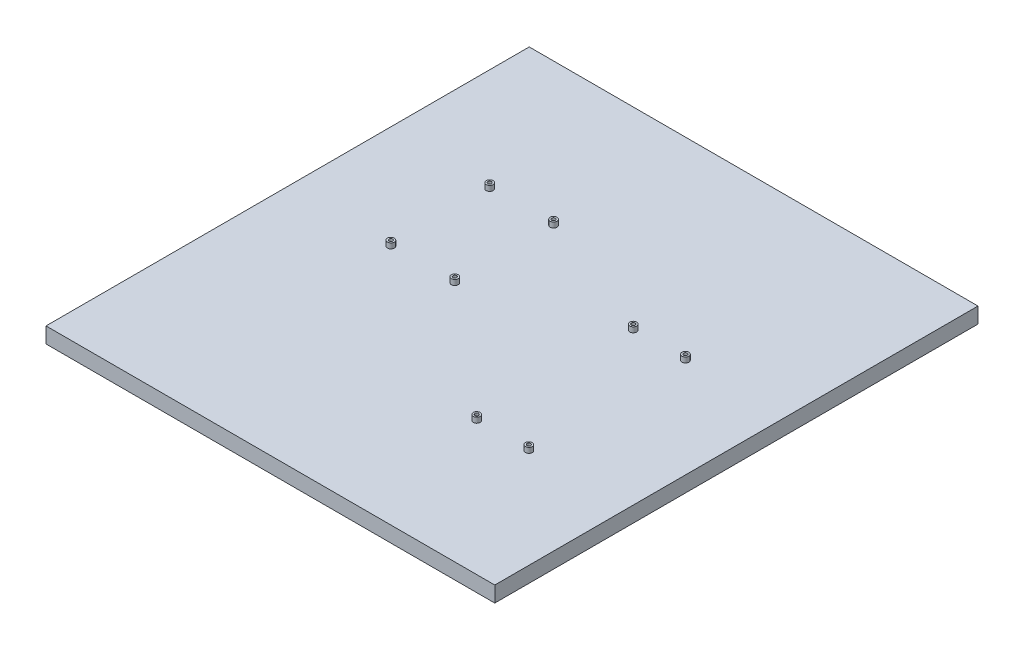
SolidWorks part; units mm, degrees
ref_plane "Front Plane" through (0, 0, 0) normal (0, 0, 1) x (1, 0, 0)
ref_plane "Top Plane" through (0, 0, 0) normal (0, 1, 0) x (1, 0, 0)
ref_plane "Right Plane" through (0, 0, 0) normal (1, 0, 0) x (0, 0, -1)
sketch "Sketch1" plane through (0, 0, 0) normal (0, 1, 0) x (1, 0, 0)
  line L1 (-215, -231.5) -> (215, -231.5)
  line L2 (-215, -231.5) -> (-215, 231.5)
  line L3 (-215, 231.5) -> (215, 231.5)
  line L4 (215, -231.5) -> (215, 231.5)
  line L5 (-215, -231.5) -> (215, 231.5) construction
  line L6 (-215, 231.5) -> (215, -231.5) construction
  point P0 (0, 0)
  dimension "D1" = 430
  dimension "D2" = 463
extrude "Boss-Extrude1" add sketch "Sketch1" along normal blind 15
sketch "Sketch6" plane through (0, 15, 0) normal (0, 1, 0) x (1, 0, 0)
  circle A0 centre (119.7933, 46.3731) radius 3.3
  circle A1 centre (69.7933, 46.3731) radius 3.3
  circle A2 centre (119.7933, -103.6269) radius 3.3
  circle A3 centre (69.7933, -103.6269) radius 3.3
sketch "Sketch7" plane through (0, 15, 0) normal (0, 1, 0) x (1, 0, 0)
  circle A0 centre (-116.3627, 94.9459) radius 3.3
  circle A1 centre (-55.3632, 95.1916) radius 3.3
  circle A2 centre (-54.9804, 0.1924) radius 3.3
  circle A3 centre (-115.98, -0.0534) radius 3.3
extrude "Boss-Extrude2" add sketch "Sketch7" along normal blind 5
sketch "Sketch8" plane through (0, 20, 0) normal (0, 1, 0) x (1, 0, 0)
  circle A0 centre (-54.9804, 0.1924) radius 1.75
  circle A1 centre (-55.3632, 95.1916) radius 1.75
  circle A2 centre (-116.3627, 94.9459) radius 1.75
  circle A3 centre (-115.98, -0.0534) radius 1.75
extrude "Cut-Extrude1" cut sketch "Sketch8" against normal blind 4
extrude "Boss-Extrude3" add sketch "Sketch6" along normal blind 5
sketch "Sketch10" plane through (0, 20, 0) normal (0, 1, 0) x (1, 0, 0)
  circle A0 centre (69.7933, 46.3731) radius 1.75
  circle A1 centre (119.7933, 46.3731) radius 1.75
  circle A2 centre (119.7933, -103.6269) radius 1.75
  circle A3 centre (69.7933, -103.6269) radius 1.75
extrude "Cut-Extrude2" cut sketch "Sketch10" against normal blind 4
sketch "Sketch12" plane through (0, 0, 0) normal (0, -1, 0) x (-1, 0, 0)
  circle A0 centre (-183.5287, -175) radius 3.8
  circle A1 centre (-203.3989, 170) radius 3.8
  circle A3 centre (-183.5287, 10) radius 3.8
  circle A4 centre (-203.3989, 10) radius 3.8
  circle A5 centre (-203.3989, -175) radius 3.8
  circle A6 centre (-183.5287, 170) radius 3.8
  circle A7 centre (206.5253, -175) radius 3.8
  circle A8 centre (206.5253, 20) radius 3.8
  circle A9 centre (186.4469, 175) radius 3.8
  circle A10 centre (206.5253, 175) radius 3.8
  circle A11 centre (186.4469, -175) radius 3.8
  circle A12 centre (186.4469, 20) radius 3.8
  circle A13 centre (160.3499, -221.5206) radius 3.8
  circle A14 centre (160.3499, -201.5484) radius 3.8
  circle A15 centre (20, -221.5206) radius 3.8
  circle A16 centre (20, -201.5484) radius 3.8
  circle A17 centre (-20, -201.5484) radius 3.8
  circle A19 centre (-20, -221.5206) radius 3.8
  circle A20 centre (-160, -221.5206) radius 3.8
  circle A21 centre (-160, -201.5484) radius 3.8
  circle A22 centre (160, 201.0677) radius 3.8
  circle A23 centre (160, 221.0364) radius 3.8
  circle A24 centre (20, 201.0677) radius 3.8
  circle A25 centre (20, 221.0364) radius 3.8
  circle A26 centre (-20, 201.0677) radius 3.8
  circle A27 centre (-20, 221.0364) radius 3.8
  circle A28 centre (-160, 201.0677) radius 3.8
  circle A29 centre (-160, 221.0364) radius 3.8
extrude "Cut-Extrude3" cut sketch "Sketch12" against normal blind 10
